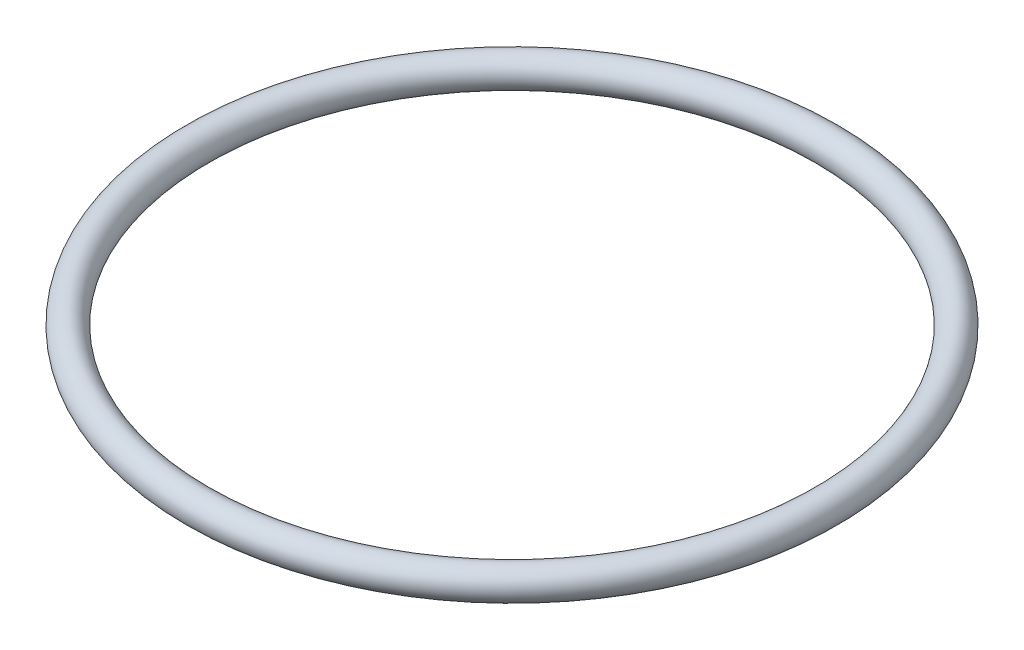
SolidWorks part; units mm, degrees
ref_plane "Front Plane" through (0, 0, 0) normal (0, 0, 1) x (1, 0, 0)
ref_plane "Top Plane" through (0, 0, 0) normal (0, 1, 0) x (1, 0, 0)
ref_plane "Right Plane" through (0, 0, 0) normal (1, 0, 0) x (0, 0, -1)
sketch "Sketch1" plane through (0, 0, 0) normal (0, 1, 0) x (1, 0, 0)
  circle A1 centre (0, 0) radius 25.2349
  dimension "B" = 50.4698
sketch "Sketch2" plane through (0, 0, 0) normal (0, 0, 1) x (1, 0, 0)
  circle A0 centre (-26.543, 0) radius 1.3081
  point P4 (-25.2349, 0)
  dimension "A" = 2.6162
sweep "Sweep1" add profiles "Sketch2" path "Sketch1"
ref_axis "Axis1" through (0, 5.2562, 0) along (0, -1, 0)
